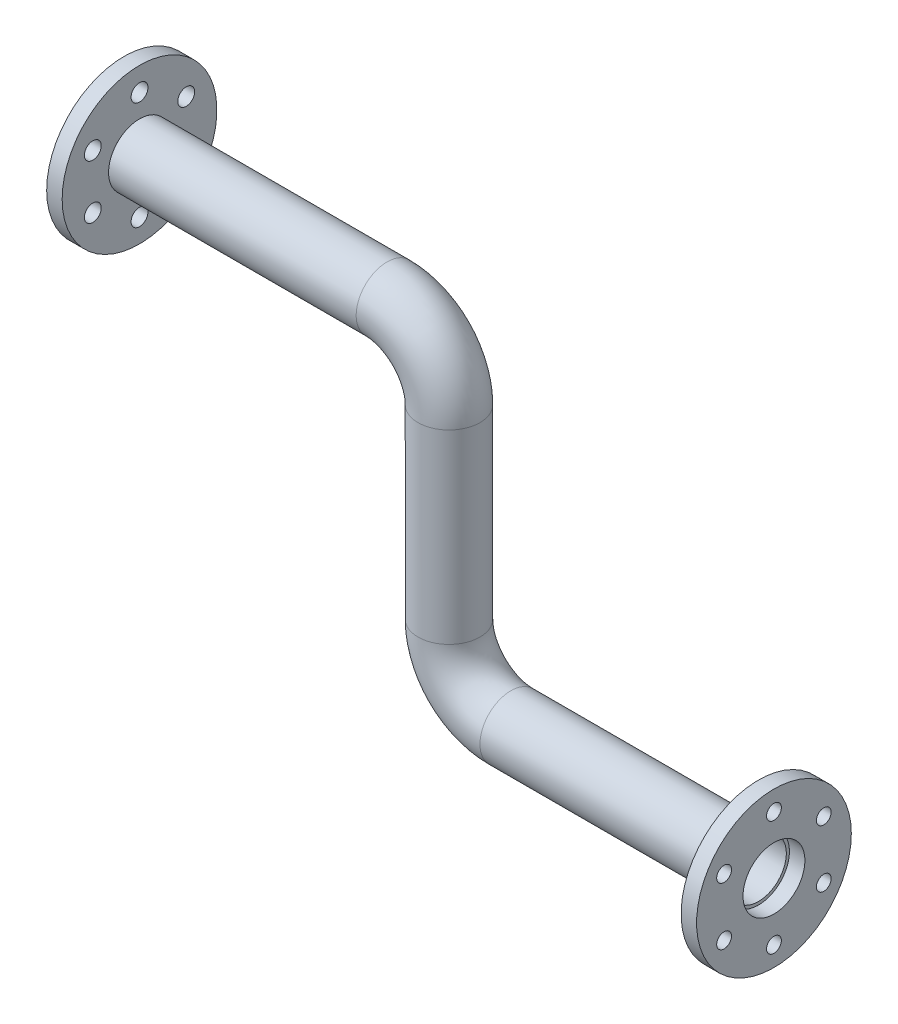
SolidWorks part; units mm, degrees
ref_plane "Front Plane" through (0, 0, 0) normal (0, 0, 1) x (1, 0, 0)
ref_plane "Top Plane" through (0, 0, 0) normal (0, 1, 0) x (1, 0, 0)
ref_plane "Right Plane" through (0, 0, 0) normal (1, 0, 0) x (0, 0, -1)
sketch "Sketch1" plane through (0, 0, 0) normal (0, 0, 1) x (1, 0, 0)
  line L0 (0, 0) -> (80, 0)
  line L1 (100, -20) -> (100, -80)
  line L2 (120, -100) -> (200, -100)
  arc A0 (100, -80) -> (120, -100) centre (120, -80) ccw
  arc A1 (80, 0) -> (100, -20) centre (80, -20) cw
  point P7 (0, 0)
  point P10 (100, -100)
  point P13 (100, 0)
  dimension "D4" = 20
  dimension "D1" = 100
  dimension "D2" = 100
  dimension "D3" = 100
sweep "Sweep1" add path "Sketch1" circular profile diameter 20 parameters "D3"=20
sketch "Sketch8" plane through (0, 0, 0) normal (-1, 0, 0) x (0, 0, 1)
  circle A0 centre (0, 0) radius 9.2233
sweep "Cut-Sweep1" cut path "Sketch1<3>" circular profile diameter 18 parameters "D3"=18
sketch "Sketch1<3>" plane through (0, 0, 0) normal (0, 0, 1) x (1, 0, 0) same geometry as "Sketch1"
ref_plane "Plane1" through (100, 0, 0) normal (1, 0, 0) x (0, 0, -1)
sketch "Sketch23" plane through (0, 0, 0) normal (-1, 0, 0) x (0, 0, 1)
  circle A0 centre (0, 0) radius 25
  circle A1 centre (0, 0) radius 10 construction
  circle A2 centre (0, 0) radius 10
  dimension "D1" = 50
extrude "Boss-Extrude2" add sketch "Sketch23" along normal blind 5 separate body
sketch "Sketch24" plane through (-5, 0, 0) normal (-1, 0, 0) x (0, 0, 1)
  circle A0 centre (0, 0) radius 17.4221 construction
  circle A1 centre (0, 17.4221) radius 2.725
extrude "Cut-Extrude2" cut sketch "Sketch24" against normal blind 5
pattern_circular "CirPattern1" count 6 over 360 about axis through (-5, 0, 0) along (-1, 0, 0) of "Cut-Extrude2"
sketch "Sketch27" plane through (200, 0, 0) normal (1, 0, 0) x (0, 0, -1)
  circle A0 centre (0, -100) radius 25
  circle A1 centre (0, -100) radius 10 construction
  circle A2 centre (0, -100) radius 10
  dimension "D1" = 50
extrude "Boss-Extrude3" add sketch "Sketch27" along normal blind 5 separate body
sketch "Sketch28" plane through (205, 0, 0) normal (1, 0, 0) x (0, 0, -1)
  circle A0 centre (0, -100) radius 18.5968 construction
  circle A1 centre (0, -81.4032) radius 2.3941
extrude "Cut-Extrude3" cut sketch "Sketch28" against normal up to next (5 mm away)
pattern_circular "CirPattern2" count 6 over 360 about axis through (205, -100, 0) along (1, 0, 0) of "Cut-Extrude3"
